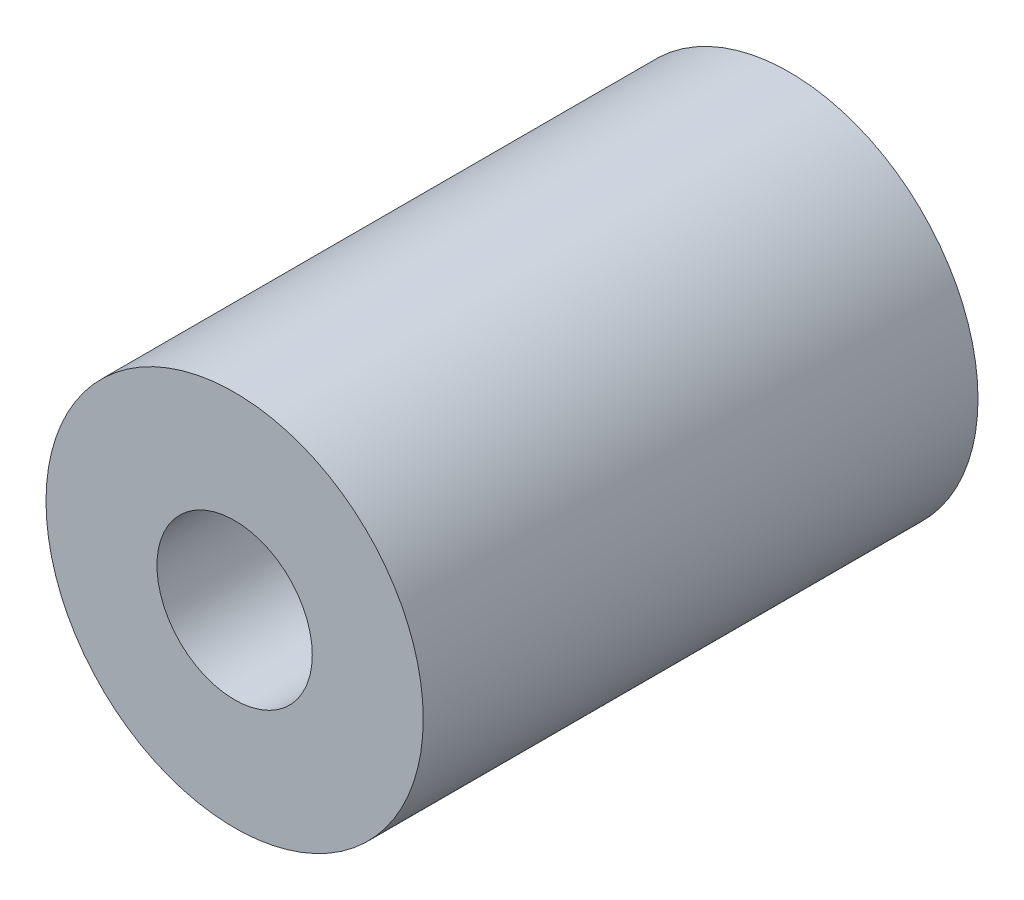
SolidWorks part; units mm, degrees
ref_plane "Front Plane" through (0, 0, 0) normal (0, 0, 1) x (1, 0, 0)
ref_plane "Top Plane" through (0, 0, 0) normal (0, 1, 0) x (1, 0, 0)
ref_plane "Right Plane" through (0, 0, 0) normal (1, 0, 0) x (0, 0, -1)
sketch "Sketch1" plane through (0, 0, 0) normal (0, 0, 1) x (1, 0, 0)
  circle A0 centre (0, 0) radius 3.4
  circle A1 centre (0, 0) radius 1.4
  dimension "D1" = 6.8
  dimension "3" = 2.8
extrude "Extrude1" add sketch "Sketch1" along normal mid plane 10
